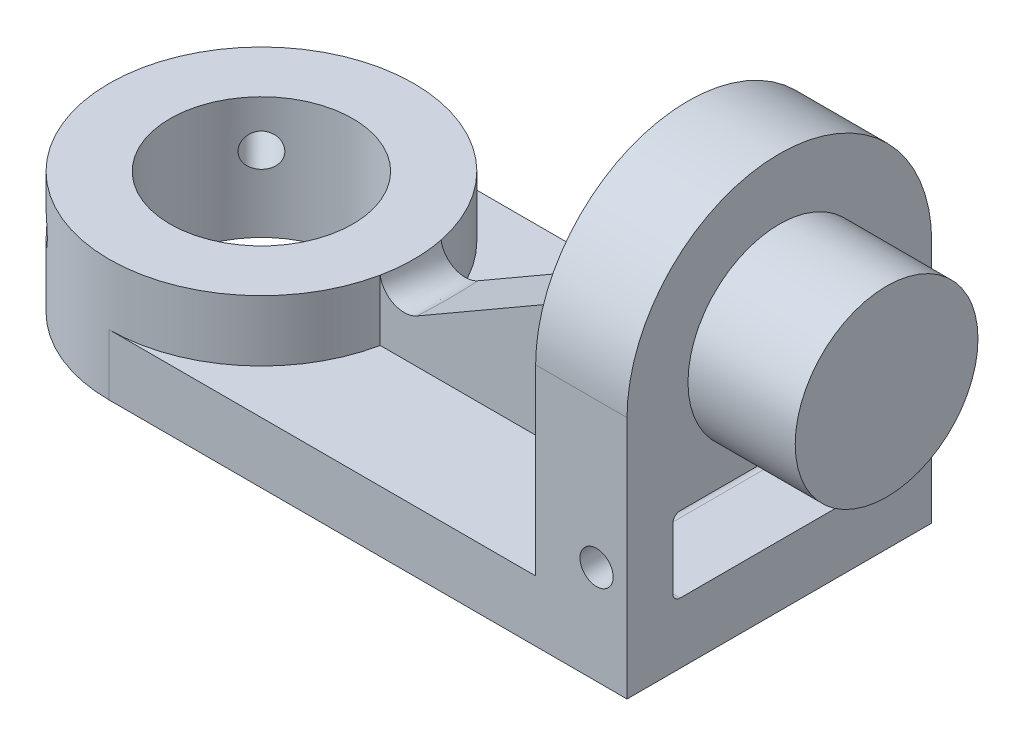
SolidWorks part; units mm, degrees
material "Alloy Steel"
ref_plane "Front Plane" through (0, 0, 0) normal (0, 0, 1) x (1, 0, 0)
ref_plane "Top Plane" through (0, 0, 0) normal (0, 1, 0) x (1, 0, 0)
ref_plane "Right Plane" through (0, 0, 0) normal (1, 0, 0) x (0, 0, -1)
sketch "Sketch2" plane through (0, 0, 0) normal (0, 1, 0) x (1, 0, 0)
  line L1 (0, -15.875) -> (53.975, -15.875)
  line L2 (0, -15.875) -> (0, 15.875)
  line L3 (0, 15.875) -> (53.975, 15.875)
  line L4 (53.975, -15.875) -> (53.975, 15.875)
  point P4 (0, 0)
  dimension "D1" = 53.975
  dimension "D2" = 31.75
extrude "Boss-Extrude2" add sketch "Sketch2" along normal blind 6.35
sketch "Sketch4" plane through (0, 0, 0) normal (0, 1, 0) x (1, 0, 0)
  circle A0 centre (0, 0) radius 15.875
  dimension "D1" = 31.75
extrude "Boss-Extrude3" add sketch "Sketch4" along normal blind 12.7
sketch "Sketch6" plane through (0, 0, 0) normal (0, 1, 0) x (1, 0, 0)
  circle A0 centre (0, 0) radius 9.525
  dimension "D1" = 19.05
extrude "Cut-Extrude2" cut sketch "Sketch6" against normal through all and the other way through all
sketch "Sketch9" plane through (0, 6.35, 0) normal (0, 1, 0) x (1, 0, 0)
  line L0 (0, -15.875) -> (53.975, -15.875) construction
  line L1 (53.975, 15.875) -> (44.45, 15.875)
  line L2 (53.975, 15.875) -> (53.975, -15.875)
  line L3 (53.975, -15.875) -> (44.45, -15.875)
  line L4 (44.45, 15.875) -> (44.45, -15.875)
  dimension "D1" = 9.525
extrude "Boss-Extrude4" add sketch "Sketch9" along normal blind 19.05
sketch "Sketch10" plane through (53.975, 0, 0) normal (1, 0, 0) x (0, 0, -1)
  line L0 (-15.875, 25.4) -> (15.875, 25.4) construction
  circle A0 centre (0, 25.4) radius 15.875
  dimension "D1" = 31.75
extrude "Boss-Extrude5" add sketch "Sketch10" against normal blind 9.525
sketch "Sketch11" plane through (53.975, 0, 0) normal (1, 0, 0) x (0, 0, -1)
  circle A0 centre (0, 25.4) radius 9.525
  dimension "D1" = 19.05
extrude "Boss-Extrude6" add sketch "Sketch11" along normal blind 11.176
sketch "Sketch12" plane through (53.975, 0, 0) normal (1, 0, 0) x (0, 0, -1)
  line L0 (-15.875, 25.4) -> (-15.875, 0) construction
  line L1 (-11.0998, 6.35) -> (11.1252, 6.35)
  line L2 (-11.0998, 6.35) -> (-11.0998, 14.224)
  line L3 (-11.0998, 14.224) -> (11.1252, 14.224)
  line L4 (11.1252, 6.35) -> (11.1252, 14.224)
  line L5 (-15.875, 0) -> (15.875, 0) construction
  dimension "D1" = 22.225
  dimension "D2" = 4.7752
  dimension "D3" = 7.874
  dimension "D4" = 6.35
extrude "Cut-Extrude3" cut sketch "Sketch12" against normal blind 8.001
fillet "Fillet1" radius 0.762 8 edges at (45.974, 14.224, -0.0127) (49.9745, 14.224, -11.1252) (45.974, 10.287, -11.1252) (45.974, 10.287, 11.0998) (49.9745, 14.224, 11.0998) (49.9745, 6.35, 11.0998) (45.974, 6.35, -0.0127) (49.9745, 6.35, -11.1252)
sketch "Sketch14" plane through (0, 0, 0) normal (0, 0, 1) x (1, 0, 0)
  line L1 (15.875, 6.35) -> (44.45, 6.35)
  line L2 (44.45, 6.35) -> (44.45, 25.4)
  line L6 (11.4544, 6.35) -> (15.875, 6.35)
  line L7 (44.45, 25.4) -> (11.4544, 6.35)
  dimension "D1" = 30
extrude "Boss-Extrude13" add sketch "Sketch14" along normal blind 3.175 and the other way blind 3.175
fillet "Fillet2" radius 2.54 1 edges at (15.875, 8.9022, 0)
hole_wizard "#29 (0.136) Diameter Hole3" positions "Sketch20" profile "Sketch21" hole size "#29" standard "ANSI Inch" end condition through all
sketch "Sketch20" plane through (0, 0, 15.875) normal (0, 0, 1) x (1, 0, 0)
  line L0 (53.975, 25.4) -> (53.975, 0) construction
  line L1 (0, 0) -> (53.975, 0) construction
  point P0 (50.8, 10.287)
  dimension "D1" = 3.175
  dimension "D2" = 10.287
sketch "Sketch21" plane through (50.8, 10.287, 15.875) normal (1, 0, 0) x (0, -1, 0)
  line L0 (0, 0) -> (0, 31.75)
  line L1 (0, 31.75) -> (1.7272, 31.75)
  line L2 (1.7272, 31.75) -> (1.7272, 0)
  line L5 (1.7272, 0) -> (0, 0)
  line L11 (0, -6.35) -> (0, 107.95) construction
  dimension "Thru Hole Dia." = 3.4544
  dimension "Thru Hole Depth" = 31.75
fillet "Fillet3" radius 0.762 2 edges at (44.45, 15.875, -3.175) (44.45, 15.875, 3.175)
ref_plane "Plane1" through (-11.2253, 0, 11.2253) normal (-0.7071, 0, 0.7071) x (0, -1, 0)
hole_wizard "#29 (0.136) Diameter Hole6" positions "Sketch25" profile "Sketch26" hole size "#29" standard "ANSI Inch" end condition up to next
sketch "Sketch25" plane through (-11.2253, 0, 11.2253) normal (-0.7071, 0, 0.7071) x (0, -1, 0)
  line L0 (-12.7, 15.875) -> (-12.7, -15.875) construction
  point P0 (-7.874, 0)
  dimension "D1" = 4.826
sketch "Sketch26" plane through (-11.2253, 7.874, 11.2253) normal (0, 1, 0) x (0.7071, 0, 0.7071)
  line L0 (0, 0) -> (0, 6.35)
  line L1 (0, 6.35) -> (1.7272, 6.35)
  line L2 (1.7272, 6.35) -> (1.7272, 0)
  line L5 (1.7272, 0) -> (0, 0)
  line L11 (0, -6.35) -> (0, 107.95) construction
  dimension "Thru Hole Dia." = 3.4544
  dimension "Thru Hole Depth" = 6.35
ref_plane "Plane2" through (-11.2253, 0, -11.2253) normal (-0.7071, 0, -0.7071) x (0, -1, 0)
hole_wizard "#29 (0.136) Diameter Hole7" positions "Sketch29" profile "Sketch30" hole size "#29" standard "ANSI Inch" end condition up to next
sketch "Sketch29" plane through (-11.2253, 0, -11.2253) normal (-0.7071, 0, -0.7071) x (0, -1, 0)
  line L0 (-12.7, 15.875) -> (-12.7, -15.875) construction
  point P0 (-7.874, 0)
  dimension "D1" = 4.826
sketch "Sketch30" plane through (-11.2253, 7.874, -11.2253) normal (0, 1, 0) x (-0.7071, 0, 0.7071)
  line L0 (0, 0) -> (0, 6.35)
  line L1 (0, 6.35) -> (1.7272, 6.35)
  line L2 (1.7272, 6.35) -> (1.7272, 0)
  line L5 (1.7272, 0) -> (0, 0)
  line L11 (0, -6.35) -> (0, 107.95) construction
  dimension "Thru Hole Dia." = 3.4544
  dimension "Thru Hole Depth" = 6.35
